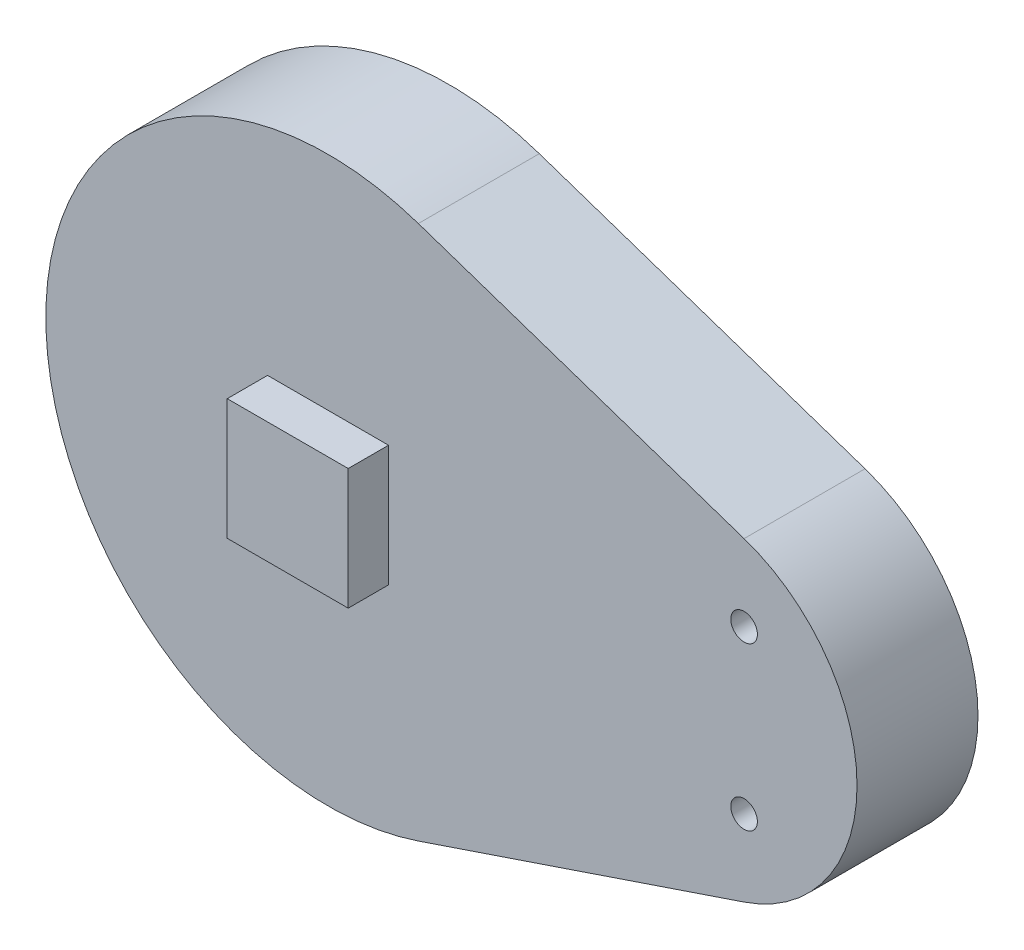
SolidWorks part; units mm, degrees
ref_plane "Płaszczyzna przednia" through (0, 0, 0) normal (0, 0, 1) x (1, 0, 0)
ref_plane "Płaszczyzna górna" through (0, 0, 0) normal (0, 1, 0) x (1, 0, 0)
ref_plane "Płaszczyzna prawa" through (0, 0, 0) normal (1, 0, 0) x (0, 0, -1)
sketch "Szkic1" plane through (0, 0, 0) normal (0, 0, 1) x (1, 0, 0)
  line L0 (45.0324, 65.8874) -> (-35.7516, 93.173)
  line L1 (31.8484, 26.8538) -> (-9.3516, 26.8538) construction
  line L2 (45.0324, -12.1798) -> (-35.7516, -39.4655)
  arc A0 (-35.7516, 93.173) -> (-35.7516, -39.4655) centre (-58.1516, 26.8538) ccw
  arc A1 (45.0324, -12.1798) -> (45.0324, 65.8874) centre (31.8484, 26.8538) ccw
  dimension "D1" = 140
  dimension "D2" = 90
extrude "Dodanie-wyciągnięcie1" add sketch "Szkic1" against normal blind 30
sketch "Szkic2" plane through (0, 0, 0) normal (0, 0, 1) x (1, 0, 0)
  line L1 (-43.1516, 11.8538) -> (-73.1516, 11.8538)
  line L2 (-43.1516, 11.8538) -> (-43.1516, 41.8538)
  line L3 (-43.1516, 41.8538) -> (-73.1516, 41.8538)
  line L4 (-73.1516, 11.8538) -> (-73.1516, 41.8538)
  line L5 (-43.1516, 11.8538) -> (-73.1516, 41.8538) construction
  line L6 (-43.1516, 41.8538) -> (-73.1516, 11.8538) construction
  point P0 (-58.1516, 26.8538)
  dimension "D1" = 30
  dimension "D2" = 30
extrude "Dodanie-wyciągnięcie2" add sketch "Szkic2" along normal blind 10
sketch "Szkic3" plane through (0, 0, -30) normal (0, 0, -1) x (-1, 0, 0)
  circle A0 centre (58.1516, 26.8538) radius 65
extrude "Dodanie-wyciągnięcie3" add sketch "Szkic3" along normal blind 3
sketch "Szkic4" plane through (0, 0, -30) normal (0, 0, -1) x (-1, 0, 0)
  line L0 (-45.0324, -12.1798) -> (-45.0324, 65.8874) construction
  line L1 (-45.0324, 65.8874) -> (-73.0484, 26.8538) construction
  line L2 (-73.0484, 26.8538) -> (-45.0324, 6.7456) construction
  arc A0 (-45.0324, 65.8874) -> (-45.0324, -12.1798) centre (-31.8484, 26.8538) ccw construction
  point P10 (-45.0324, 6.7456)
hole_wizard "Pogłębienie walcowe pod M6 Śrubę z łbem stożkowym ściętym1" positions "Szkic 3D1" profile "Szkic5" counterbore size "M6" standard "ISO" end condition up to next
sketch3d "Szkic 3D1"
  point P0 (45.0324, 6.7456, -30)
sketch "Szkic5" plane through (45.0324, 6.7456, -30) normal (1, 0, 0) x (0, 1, 0)
  line L0 (0, 0) -> (0, 30)
  line L1 (0, 30) -> (3.3, 30)
  line L3 (3.3, 30) -> (3.3, 4.6)
  line L4 (3.3, 4.6) -> (6.5, 4.6)
  line L5 (6.5, 4.6) -> (6.5, 0)
  line L7 (6.5, 0) -> (0, 0)
  line L11 (0, -6.35) -> (0, 107.95) construction
  dimension "Średnica otworu na wylot" = 6.6
  dimension "Głębokość otworu na wylot" = 30
  dimension "Średnica pogłębienia walcowego" = 13
  dimension "Głębokość pogłębienia walcowego" = 4.6
sketch "Szkic6" plane through (0, 0, -30) normal (0, 0, -1) x (-1, 0, 0)
  line L0 (-45.0324, -12.1798) -> (-45.0324, 65.8874) construction
  line L1 (-45.0324, 65.8874) -> (-73.0484, 26.8538) construction
  line L2 (-73.0484, 26.8538) -> (-45.0324, 46.962) construction
  line L5 (-73.0484, 26.8538) -> (-45.0324, 6.7456) construction
  line L6 (-45.0324, 6.7456) -> (-45.0324, 26.8538) construction
  line L7 (-45.0324, 26.8538) -> (-73.0484, 26.8538) construction
  point P8 (-45.0324, 46.962)
hole_wizard "Pogłębienie walcowe pod M6 Śrubę z łbem stożkowym ściętym2" positions "Szkic 3D2" profile "Szkic7" counterbore size "M6" standard "ISO" end condition up to next
sketch3d "Szkic 3D2"
  point P0 (45.0324, 46.962, -30)
sketch "Szkic7" plane through (45.0324, 46.962, -30) normal (1, 0, 0) x (0, 1, 0)
  line L0 (0, 0) -> (0, 30)
  line L1 (0, 30) -> (3.3, 30)
  line L3 (3.3, 30) -> (3.3, 4.6)
  line L4 (3.3, 4.6) -> (6.5, 4.6)
  line L5 (6.5, 4.6) -> (6.5, 0)
  line L7 (6.5, 0) -> (0, 0)
  line L11 (0, -6.35) -> (0, 107.95) construction
  dimension "Średnica otworu na wylot" = 6.6
  dimension "Głębokość otworu na wylot" = 30
  dimension "Średnica pogłębienia walcowego" = 13
  dimension "Głębokość pogłębienia walcowego" = 4.6
fillet "Zaokrąglenie2" radius 1 2 edges at (38.5324, 46.962, -30) (38.5324, 6.7456, -30)
sketch "Szkic8" plane through (0, 0, -33) normal (0, 0, -1) x (-1, 0, 0)
  circle A0 centre (58.1516, 26.8538) radius 30
extrude "Dodanie-wyciągnięcie4" add sketch "Szkic8" along normal blind 10
